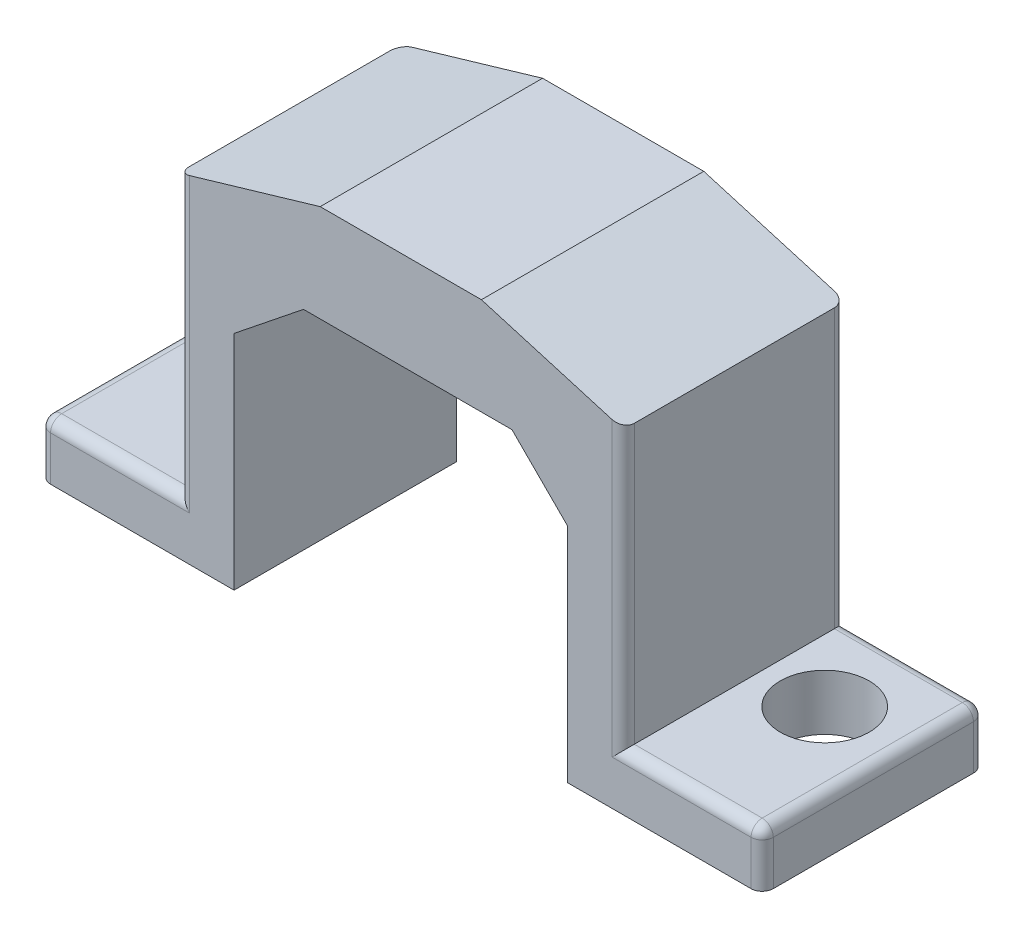
SolidWorks part; units mm, degrees
ref_plane "Ebene vorne" through (0, 0, 0) normal (0, 0, 1) x (1, 0, 0)
ref_plane "Ebene oben" through (0, 0, 0) normal (0, 1, 0) x (1, 0, 0)
ref_plane "Ebene rechts" through (0, 0, 0) normal (1, 0, 0) x (0, 0, -1)
sketch "Skizze1" plane through (0, 0, 0) normal (0, 0, 1) x (1, 0, 0)
  line L0 (0, 0) -> (7, 0)
  line L1 (7, 0) -> (7, 10)
  line L2 (7, 10) -> (19, 10)
  line L3 (19, 10) -> (19, 0)
  line L4 (19, 0) -> (26, 0)
  line L5 (26, 0) -> (26, 2)
  line L6 (26, 2) -> (21, 2)
  line L7 (21, 2) -> (21, 12)
  line L9 (5, 12) -> (5, 2)
  line L10 (5, 2) -> (0, 2)
  line L11 (0, 2) -> (0, 0)
  line L14 (15.9, 13.5) -> (21, 12)
  line L15 (5, 12) -> (10.1, 13.5)
  line L16 (10.1, 13.5) -> (15.9, 13.5)
  dimension "D1" = 12
  dimension "D2" = 10
  dimension "D3" = 7
  dimension "D4" = 7
  dimension "D5" = 5.1
  dimension "D6" = 16
  dimension "D7" = 10
  dimension "D8" = 10
  dimension "D9" = 2
  dimension "D10" = 2
  dimension "D11" = 2
  dimension "D12" = 3.5
  dimension "D13" = 5.1
extrude "Grundkörper" add sketch "Skizze1" along normal blind 8
sketch "Skizze4" plane through (0, 0, 0) normal (0, -1, 0) x (1, 0, 0)
  line L0 (26, 8) -> (26, 0) construction
  line L1 (19, 0) -> (26, 0) construction
  circle A0 centre (23.25, 3) radius 1.6
  dimension "D1" = 3.2
  dimension "D3" = 3
  dimension "D2" = 2.75
extrude "Schrauben-Bohrung" cut sketch "Skizze4" against normal blind 3
ref_plane "Ebene1" through (0, 2, 0) normal (0, -1, 0) x (-1, 0, 0)
ref_plane "Ebene2" through (13, 0, 0) normal (1, 0, 0) x (0, 0, -1)
fillet "Verrundung1" radius 0.4 13 edges at (23.5, 2, 0) (23.5, 2, 8) (2.5, 2, 0) (2.5, 2, 8) (5, 7, 8) (5, 7, 0) (21, 7, 8) (21, 7, 0) (26, 1, 0) (26, 1, 8) (26, 2, 4) (0, 2, 4) (0, 1, 8)
ref_plane "Ebene3" through (25.6, 1.6, 8) normal (-1, 0, 0) x (0, 0, 1)
sketch "Skizze8" plane through (0, 0, 8) normal (0, 0, 1) x (1, 0, 0)
  line L0 (9.5, 10) -> (7, 8)
  line L1 (7, 10) -> (19, 10) construction
  line L2 (7, 0) -> (7, 10) construction
  line L3 (7, 8) -> (7, 10)
  line L4 (7, 10) -> (9.5, 10)
  line L5 (17, 10) -> (19, 10)
  line L6 (19, 10) -> (19, 8)
  line L7 (19, 10) -> (19, 0) construction
  line L8 (19, 8) -> (17, 10)
  dimension "D1" = 2
  dimension "D2" = 2
extrude "Dreiecke_seitlich_Halter" add sketch "Skizze8" against normal blind 0.75
ref_plane "Ebene4" through (0, 0, 5) normal (0, 0, 1) x (1, 0, 0)
mirror "Spiegeln_seitlich_Halter" about plane through (0, 0, 5) normal (0, 0, 1) of "Dreiecke_seitlich_Halter"
mirror "Spiegeln5" about plane through (13, 0, 0) normal (1, 0, 0) of "Schrauben-Bohrung"
